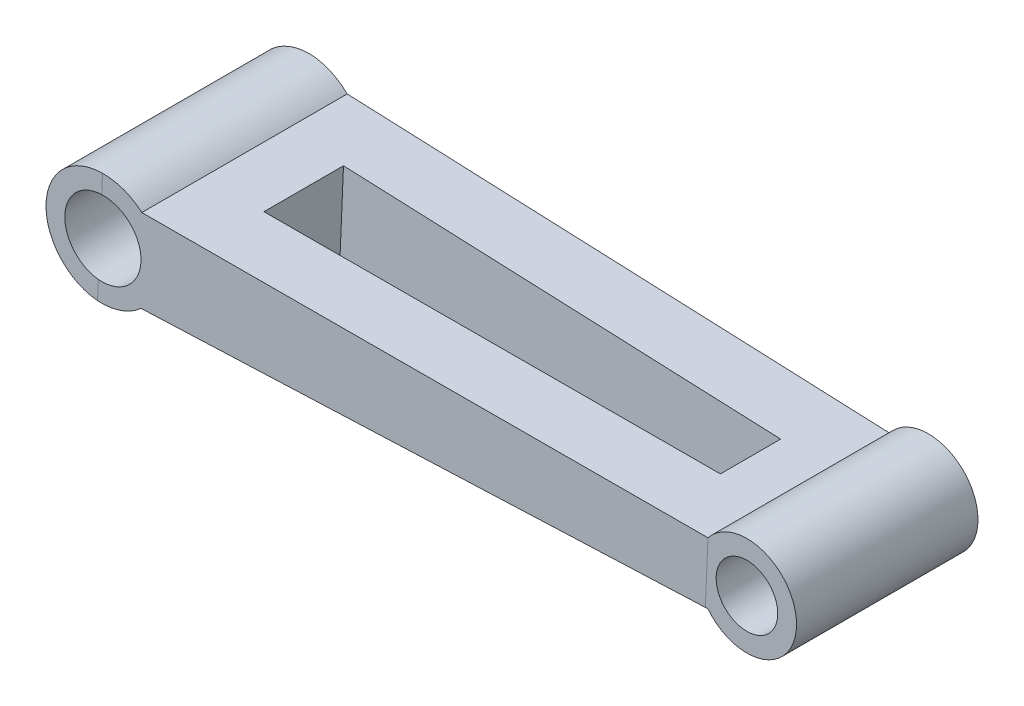
SolidWorks part; units mm, degrees
ref_plane "Front Plane" through (0, 0, 0) normal (0, 0, 1) x (1, 0, 0)
ref_plane "Top Plane" through (0, 0, 0) normal (0, 1, 0) x (1, 0, 0)
ref_plane "Right Plane" through (0, 0, 0) normal (1, 0, 0) x (0, 0, -1)
sketch "Sketch1" plane through (0, 0, 0) normal (0, 0, 1) x (1, 0, 0)
  line L4 (161.7624, 18) -> (-162.0253, 24.1638)
  line L5 (161.7624, -18) -> (-162.5, -24.5967)
  circle A1 centre (-184.5, 0) radius 22
  arc A2 (161.7624, -18) -> (161.7624, 18) centre (184.5, 0) ccw
  circle A3 centre (184.5, 0) radius 18
  arc A4 (-162.0253, 24.1638) -> (-162.5, -24.5967) centre (-184.5, 0) ccw
  dimension "D4" = 44
  dimension "D5" = 58
  dimension "D6" = 36
  dimension "D1" = 66
extrude "Boss-Extrude1" add sketch "Sketch1" along normal blind 121 contours A2 A3 A1 region at (-7.9602, -0.0912, 0)
sketch "Sketch3" plane through (1.0813, 24.9607, 0) normal (0.0433, 0.9991, 0) x (0.9991, -0.0433, 0)
  line L3 (160.8318, -60.5) -> (160.8318, -7.5)
  line L5 (160.8318, -121) -> (160.8318, 0) construction
  line L6 (160.8318, -60.5) -> (160.8318, -113.5)
  line L8 (160.8318, -7.5) -> (-185.7553, 0)
  line L9 (-185.7553, 0) -> (160.8318, 0) construction
  line L10 (160.8318, -113.5) -> (-185.7553, -121)
  line L11 (-185.7553, 0) -> (-286.5834, 0)
  line L14 (-286.5834, 0) -> (-286.5834, 54.4588)
  line L17 (-286.5834, 54.4588) -> (275.2391, 54.4588)
  line L18 (275.2391, 54.4588) -> (275.2391, -7.5)
  line L19 (275.2391, -7.5) -> (160.8318, -7.5)
  line L20 (160.8318, -113.5) -> (275.2391, -113.5)
  line L21 (275.2391, -113.5) -> (275.2391, -184.897)
  line L22 (275.2391, -184.897) -> (-286.5834, -184.897)
  line L23 (-286.5834, -184.897) -> (-286.5834, -121)
  line L24 (-286.5834, -121) -> (-185.7553, -121)
  dimension "D4" = 53
  dimension "D3" = 53
extrude "Cut-Extrude2" cut sketch "Sketch3" against normal blind 121 and the other way blind 121 contours L19 L18 L17 L14 L11 | L8 | L10 | L24 L23 L22 L21 L20 region at (3.2903, 24.865, -25.2382) region at (2.1929, 24.9125, 150.9671)
sketch "Sketch4" plane through (1.0813, 24.9607, 0) normal (0.0433, 0.9991, 0) x (0.9991, -0.0433, 0)
  line L2 (-186.5342, -35.9916) -> (160.0529, -43.4916)
  line L3 (-128.3271, -37.2512) -> (132.6729, -42.8991)
  line L4 (-128.3271, -60.5) -> (132.6729, -60.5)
  line L5 (-186.5342, -85.0084) -> (160.0529, -77.5084)
  line L6 (-128.3271, -83.7488) -> (132.6729, -78.1009)
  line L8 (-128.3271, -60.5) -> (-128.3271, -37.2512)
  line L9 (-128.3271, -60.5) -> (-128.3271, -83.7488)
  line L10 (132.6729, -60.5) -> (132.6729, -42.8991)
  line L11 (132.6729, -60.5) -> (132.6729, -78.1009)
  dimension "D3" = 261
  dimension "D1" = 36
  dimension "D2" = 36
extrude "Cut-Extrude3" cut sketch "Sketch4" against normal blind 121 and the other way blind 121 contours L4 L10 L3 L8 | L11 L4 L9 L6 region at (-2.7566, 25.1269, 50.2225) region at (-2.7566, 25.1269, 70.7775)
